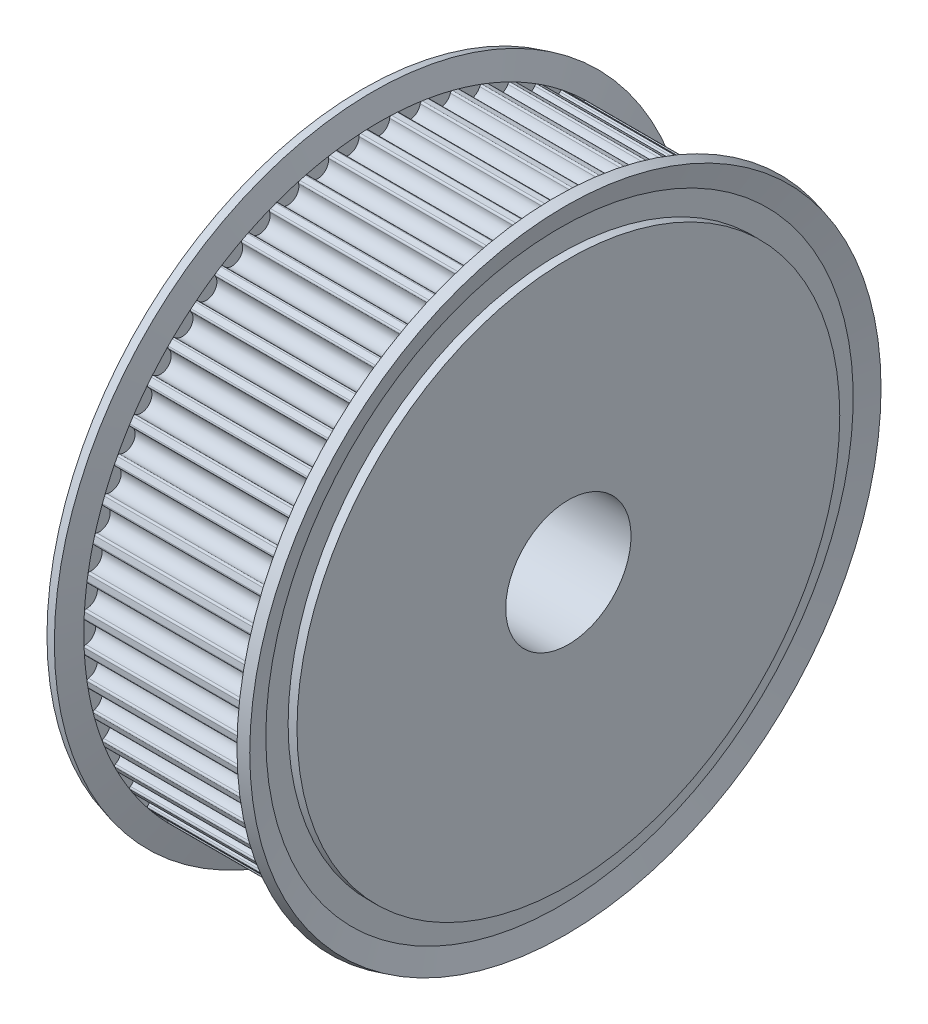
SolidWorks part; units mm, degrees
ref_plane "Front Plane" through (0, 0, 0) normal (0, 0, 1) x (1, 0, 0)
ref_plane "Top Plane" through (0, 0, 0) normal (0, 1, 0) x (1, 0, 0)
ref_plane "Right Plane" through (0, 0, 0) normal (1, 0, 0) x (0, 0, -1)
ref_plane "Plane1" through (0, 0, 0) normal (0, 0, 1) x (1, 0, 0)
sketch "Sketch1" plane through (0, 0, 0) normal (0, 0, 1) x (1, 0, 0)
  line L0 (0, 0) -> (0, 26)
  line L1 (0, 26) -> (0.85, 26)
  line L2 (0.85, 26) -> (0.85, 28.1383)
  line L3 (0.85, 28.1383) -> (0.2865, 30.2412)
  line L4 (0.2865, 30.2412) -> (1.2525, 30.5)
  line L5 (1.2525, 30.5) -> (1.85, 28.27)
  line L6 (1.85, 28.27) -> (18.15, 28.27)
  line L7 (18.15, 28.27) -> (18.7475, 30.5)
  line L8 (18.7475, 30.5) -> (19.7135, 30.2412)
  line L9 (19.7135, 30.2412) -> (19.15, 28.1383)
  line L10 (19.15, 28.1383) -> (19.15, 26)
  line L11 (19.15, 26) -> (20, 26)
  line L12 (20, 26) -> (20, 0)
  line L13 (20, 0) -> (0, 0)
  line L14 (20, 0) -> (0, 0) construction
revolve "Revolve1" add sketch "Sketch1" angle 360 about L14 reverse direction yes
ref_plane "Plane2" through (10, 0, 0) normal (1, 0, 0) x (0, 0, -1)
sketch "Sketch2" plane through (10, 0, 0) normal (1, 0, 0) x (0, 0, -1)
  line L0 (-1.2204, 28.624) -> (-1.2042, 28.2443)
  line L1 (1.2042, 28.2443) -> (1.2204, 28.624)
  arc A0 (-1.2042, 28.2443) -> (-1.0274, 28.0866) centre (-1.1969, 28.0745) cw
  arc A1 (-1.0274, 28.0866) -> (1.0274, 28.0866) centre (0, 28.16) ccw
  arc A2 (1.0274, 28.0866) -> (1.2042, 28.2443) centre (1.1969, 28.0745) cw
  arc A3 (1.2204, 28.624) -> (-1.2204, 28.624) centre (0, 0) ccw
extrude "Cut-Extrude1" cut sketch "Sketch2" against normal blind 8.15 and the other way blind 8.15
ref_plane "Plane3" through (10, 0, 0) normal (1, 0, 0) x (0, 0, -1)
sketch "Sketch3" plane through (10, 0, 0) normal (1, 0, 0) x (0, 0, -1)
  line L0 (-4.2057, 28.3396) -> (-4.1499, 27.9637)
  line L1 (-1.7547, 28.2155) -> (-1.7783, 28.5948)
  arc A0 (-4.1499, 27.9637) -> (-3.9576, 27.8254) centre (-4.125, 27.7956) cw
  arc A1 (-3.9576, 27.8254) -> (-1.9141, 28.0401) centre (-2.9435, 28.0057) ccw
  arc A2 (-1.9141, 28.0401) -> (-1.7547, 28.2155) centre (-1.7442, 28.0458) cw
  arc A3 (-1.7783, 28.5948) -> (-4.2057, 28.3396) centre (0, 0) ccw
extrude "Cut-Extrude2" cut sketch "Sketch3" against normal blind 8.15 and the other way blind 8.15
ref_plane "Plane4" through (10, 0, 0) normal (1, 0, 0) x (0, 0, -1)
sketch "Sketch4" plane through (10, 0, 0) normal (1, 0, 0) x (0, 0, -1)
  line L0 (-7.145, 27.7448) -> (-7.0502, 27.3768)
  line L1 (-4.6945, 27.8775) -> (-4.7576, 28.2522)
  arc A0 (-7.0502, 27.3768) -> (-6.8445, 27.2592) centre (-7.0078, 27.2121) cw
  arc A1 (-6.8445, 27.2592) -> (-4.8346, 27.6865) centre (-5.8548, 27.5446) ccw
  arc A2 (-4.8346, 27.6865) -> (-4.6945, 27.8775) centre (-4.6662, 27.7099) cw
  arc A3 (-4.7576, 28.2522) -> (-7.145, 27.7448) centre (0, 0) ccw
extrude "Cut-Extrude3" cut sketch "Sketch4" against normal blind 8.15 and the other way blind 8.15
ref_plane "Plane5" through (10, 0, 0) normal (1, 0, 0) x (0, 0, -1)
sketch "Sketch5" plane through (10, 0, 0) normal (1, 0, 0) x (0, 0, -1)
  line L0 (-10.0059, 26.8459) -> (-9.8732, 26.4898)
  line L1 (-7.5827, 27.2341) -> (-7.6847, 27.6002)
  arc A0 (-9.8732, 26.4898) -> (-9.6563, 26.3945) centre (-9.8139, 26.3306) cw
  arc A1 (-9.6563, 26.3945) -> (-7.7021, 27.0294) centre (-8.7019, 26.7818) ccw
  arc A2 (-7.7021, 27.0294) -> (-7.5827, 27.2341) centre (-7.5371, 27.0703) cw
  arc A3 (-7.6847, 27.6002) -> (-10.0059, 26.8459) centre (0, 0) ccw
extrude "Cut-Extrude4" cut sketch "Sketch5" against normal blind 8.15 and the other way blind 8.15
ref_plane "Plane6" through (10, 0, 0) normal (1, 0, 0) x (0, 0, -1)
sketch "Sketch6" plane through (10, 0, 0) normal (1, 0, 0) x (0, 0, -1)
  line L0 (-12.7573, 25.6529) -> (-12.5881, 25.3127)
  line L1 (-10.3879, 26.2923) -> (-10.5276, 26.6457)
  arc A0 (-12.5881, 25.3127) -> (-12.3624, 25.2405) centre (-12.5124, 25.1605) cw
  arc A1 (-12.3624, 25.2405) -> (-10.4853, 26.0763) centre (-11.4537, 25.7254) ccw
  arc A2 (-10.4853, 26.0763) -> (-10.3879, 26.2923) centre (-10.3255, 26.1342) cw
  arc A3 (-10.5276, 26.6457) -> (-12.7573, 25.6529) centre (0, 0) ccw
extrude "Cut-Extrude5" cut sketch "Sketch6" against normal blind 8.15 and the other way blind 8.15
ref_plane "Plane7" through (10, 0, 0) normal (1, 0, 0) x (0, 0, -1)
sketch "Sketch7" plane through (10, 0, 0) normal (1, 0, 0) x (0, 0, -1)
  line L0 (-15.3689, 24.1789) -> (-15.165, 23.8582)
  line L1 (-13.0793, 25.0624) -> (-13.2551, 25.3993)
  arc A0 (-15.165, 23.8582) -> (-14.933, 23.81) centre (-15.0738, 23.7148) cw
  arc A1 (-14.933, 23.81) -> (-13.1536, 24.8374) centre (-14.08, 24.3873) ccw
  arc A2 (-13.1536, 24.8374) -> (-13.0793, 25.0624) centre (-13.0007, 24.9117) cw
  arc A3 (-13.2551, 25.3993) -> (-15.3689, 24.1789) centre (0, 0) ccw
extrude "Cut-Extrude6" cut sketch "Sketch7" against normal blind 8.15 and the other way blind 8.15
ref_plane "Plane8" through (10, 0, 0) normal (1, 0, 0) x (0, 0, -1)
sketch "Sketch8" plane through (10, 0, 0) normal (1, 0, 0) x (0, 0, -1)
  line L0 (-17.8121, 22.44) -> (-17.5758, 22.1423)
  line L1 (-15.6274, 23.558) -> (-15.8375, 23.8746)
  arc A0 (-17.5758, 22.1423) -> (-17.3401, 22.1187) centre (-17.4701, 22.0092) cw
  arc A1 (-17.3401, 22.1187) -> (-15.6777, 23.3264) centre (-16.552, 22.7819) ccw
  arc A2 (-15.6777, 23.3264) -> (-15.6274, 23.558) centre (-15.5334, 23.4163) cw
  arc A3 (-15.8375, 23.8746) -> (-17.8121, 22.44) centre (0, 0) ccw
extrude "Cut-Extrude7" cut sketch "Sketch8" against normal blind 8.15 and the other way blind 8.15
ref_plane "Plane9" through (10, 0, 0) normal (1, 0, 0) x (0, 0, -1)
sketch "Sketch9" plane through (10, 0, 0) normal (1, 0, 0) x (0, 0, -1)
  line L0 (-20.0601, 20.4552) -> (-19.794, 20.1839)
  line L1 (-18.0043, 21.7954) -> (-18.2463, 22.0884)
  arc A0 (-19.794, 20.1839) -> (-19.5571, 20.185) centre (-19.675, 20.0625) cw
  arc A1 (-19.5571, 20.185) -> (-18.0301, 21.5599) centre (-18.8427, 20.927) ccw
  arc A2 (-18.0301, 21.5599) -> (-18.0043, 21.7954) centre (-17.896, 21.6643) cw
  arc A3 (-18.2463, 22.0884) -> (-20.0601, 20.4552) centre (0, 0) ccw
extrude "Cut-Extrude8" cut sketch "Sketch9" against normal blind 8.15 and the other way blind 8.15
ref_plane "Plane10" through (10, 0, 0) normal (1, 0, 0) x (0, 0, -1)
sketch "Sketch10" plane through (10, 0, 0) normal (1, 0, 0) x (0, 0, -1)
  line L0 (-22.0884, 18.2463) -> (-21.7954, 18.0043)
  line L1 (-20.1839, 19.794) -> (-20.4552, 20.0601)
  arc A0 (-21.7954, 18.0043) -> (-21.5599, 18.0301) centre (-21.6643, 17.896) cw
  arc A1 (-21.5599, 18.0301) -> (-20.185, 19.5571) centre (-20.927, 18.8427) ccw
  arc A2 (-20.185, 19.5571) -> (-20.1839, 19.794) centre (-20.0625, 19.675) cw
  arc A3 (-20.4552, 20.0601) -> (-22.0884, 18.2463) centre (0, 0) ccw
extrude "Cut-Extrude9" cut sketch "Sketch10" against normal blind 8.15 and the other way blind 8.15
ref_plane "Plane11" through (10, 0, 0) normal (1, 0, 0) x (0, 0, -1)
sketch "Sketch11" plane through (10, 0, 0) normal (1, 0, 0) x (0, 0, -1)
  line L0 (-23.8746, 15.8375) -> (-23.558, 15.6274)
  line L1 (-22.1423, 17.5758) -> (-22.44, 17.8121)
  arc A0 (-23.558, 15.6274) -> (-23.3264, 15.6777) centre (-23.4163, 15.5334) cw
  arc A1 (-23.3264, 15.6777) -> (-22.1187, 17.3401) centre (-22.7819, 16.552) ccw
  arc A2 (-22.1187, 17.3401) -> (-22.1423, 17.5758) centre (-22.0092, 17.4701) cw
  arc A3 (-22.44, 17.8121) -> (-23.8746, 15.8375) centre (0, 0) ccw
extrude "Cut-Extrude10" cut sketch "Sketch11" against normal blind 8.15 and the other way blind 8.15
ref_plane "Plane12" through (10, 0, 0) normal (1, 0, 0) x (0, 0, -1)
sketch "Sketch12" plane through (10, 0, 0) normal (1, 0, 0) x (0, 0, -1)
  line L0 (-25.3993, 13.2551) -> (-25.0624, 13.0793)
  line L1 (-23.8582, 15.165) -> (-24.1789, 15.3689)
  arc A0 (-25.0624, 13.0793) -> (-24.8374, 13.1536) centre (-24.9117, 13.0007) cw
  arc A1 (-24.8374, 13.1536) -> (-23.81, 14.933) centre (-24.3873, 14.08) ccw
  arc A2 (-23.81, 14.933) -> (-23.8582, 15.165) centre (-23.7148, 15.0738) cw
  arc A3 (-24.1789, 15.3689) -> (-25.3993, 13.2551) centre (0, 0) ccw
extrude "Cut-Extrude11" cut sketch "Sketch12" against normal blind 8.15 and the other way blind 8.15
ref_plane "Plane13" through (10, 0, 0) normal (1, 0, 0) x (0, 0, -1)
sketch "Sketch13" plane through (10, 0, 0) normal (1, 0, 0) x (0, 0, -1)
  line L0 (-26.6457, 10.5276) -> (-26.2923, 10.3879)
  line L1 (-25.3127, 12.5881) -> (-25.6529, 12.7573)
  arc A0 (-26.2923, 10.3879) -> (-26.0763, 10.4853) centre (-26.1342, 10.3255) cw
  arc A1 (-26.0763, 10.4853) -> (-25.2405, 12.3624) centre (-25.7254, 11.4537) ccw
  arc A2 (-25.2405, 12.3624) -> (-25.3127, 12.5881) centre (-25.1605, 12.5124) cw
  arc A3 (-25.6529, 12.7573) -> (-26.6457, 10.5276) centre (0, 0) ccw
extrude "Cut-Extrude12" cut sketch "Sketch13" against normal blind 8.15 and the other way blind 8.15
ref_plane "Plane14" through (10, 0, 0) normal (1, 0, 0) x (0, 0, -1)
sketch "Sketch14" plane through (10, 0, 0) normal (1, 0, 0) x (0, 0, -1)
  line L0 (-27.6002, 7.6847) -> (-27.2341, 7.5827)
  line L1 (-26.4898, 9.8732) -> (-26.8459, 10.0059)
  arc A0 (-27.2341, 7.5827) -> (-27.0294, 7.7021) centre (-27.0703, 7.5371) cw
  arc A1 (-27.0294, 7.7021) -> (-26.3945, 9.6563) centre (-26.7818, 8.7019) ccw
  arc A2 (-26.3945, 9.6563) -> (-26.4898, 9.8732) centre (-26.3306, 9.8139) cw
  arc A3 (-26.8459, 10.0059) -> (-27.6002, 7.6847) centre (0, 0) ccw
extrude "Cut-Extrude13" cut sketch "Sketch14" against normal blind 8.15 and the other way blind 8.15
ref_plane "Plane15" through (10, 0, 0) normal (1, 0, 0) x (0, 0, -1)
sketch "Sketch15" plane through (10, 0, 0) normal (1, 0, 0) x (0, 0, -1)
  line L0 (-28.2522, 4.7576) -> (-27.8775, 4.6945)
  line L1 (-27.3768, 7.0502) -> (-27.7448, 7.145)
  arc A0 (-27.8775, 4.6945) -> (-27.6865, 4.8346) centre (-27.7099, 4.6662) cw
  arc A1 (-27.6865, 4.8346) -> (-27.2592, 6.8445) centre (-27.5446, 5.8548) ccw
  arc A2 (-27.2592, 6.8445) -> (-27.3768, 7.0502) centre (-27.2121, 7.0078) cw
  arc A3 (-27.7448, 7.145) -> (-28.2522, 4.7576) centre (0, 0) ccw
extrude "Cut-Extrude14" cut sketch "Sketch15" against normal blind 8.15 and the other way blind 8.15
ref_plane "Plane16" through (10, 0, 0) normal (1, 0, 0) x (0, 0, -1)
sketch "Sketch16" plane through (10, 0, 0) normal (1, 0, 0) x (0, 0, -1)
  line L0 (-28.5948, 1.7783) -> (-28.2155, 1.7547)
  line L1 (-27.9637, 4.1499) -> (-28.3396, 4.2057)
  arc A0 (-28.2155, 1.7547) -> (-28.0401, 1.9141) centre (-28.0458, 1.7442) cw
  arc A1 (-28.0401, 1.9141) -> (-27.8254, 3.9576) centre (-28.0057, 2.9435) ccw
  arc A2 (-27.8254, 3.9576) -> (-27.9637, 4.1499) centre (-27.7956, 4.125) cw
  arc A3 (-28.3396, 4.2057) -> (-28.5948, 1.7783) centre (0, 0) ccw
extrude "Cut-Extrude15" cut sketch "Sketch16" against normal blind 8.15 and the other way blind 8.15
ref_plane "Plane17" through (10, 0, 0) normal (1, 0, 0) x (0, 0, -1)
sketch "Sketch17" plane through (10, 0, 0) normal (1, 0, 0) x (0, 0, -1)
  line L0 (-28.624, -1.2204) -> (-28.2443, -1.2042)
  line L1 (-28.2443, 1.2042) -> (-28.624, 1.2204)
  arc A0 (-28.2443, -1.2042) -> (-28.0866, -1.0274) centre (-28.0745, -1.1969) cw
  arc A1 (-28.0866, -1.0274) -> (-28.0866, 1.0274) centre (-28.16, 0) ccw
  arc A2 (-28.0866, 1.0274) -> (-28.2443, 1.2042) centre (-28.0745, 1.1969) cw
  arc A3 (-28.624, 1.2204) -> (-28.624, -1.2204) centre (0, 0) ccw
extrude "Cut-Extrude16" cut sketch "Sketch17" against normal blind 8.15 and the other way blind 8.15
ref_plane "Plane18" through (10, 0, 0) normal (1, 0, 0) x (0, 0, -1)
sketch "Sketch18" plane through (10, 0, 0) normal (1, 0, 0) x (0, 0, -1)
  line L0 (-28.3396, -4.2057) -> (-27.9637, -4.1499)
  line L1 (-28.2155, -1.7547) -> (-28.5948, -1.7783)
  arc A0 (-27.9637, -4.1499) -> (-27.8254, -3.9576) centre (-27.7956, -4.125) cw
  arc A1 (-27.8254, -3.9576) -> (-28.0401, -1.9141) centre (-28.0057, -2.9435) ccw
  arc A2 (-28.0401, -1.9141) -> (-28.2155, -1.7547) centre (-28.0458, -1.7442) cw
  arc A3 (-28.5948, -1.7783) -> (-28.3396, -4.2057) centre (0, 0) ccw
extrude "Cut-Extrude17" cut sketch "Sketch18" against normal blind 8.15 and the other way blind 8.15
ref_plane "Plane19" through (10, 0, 0) normal (1, 0, 0) x (0, 0, -1)
sketch "Sketch19" plane through (10, 0, 0) normal (1, 0, 0) x (0, 0, -1)
  line L0 (-27.7448, -7.145) -> (-27.3768, -7.0502)
  line L1 (-27.8775, -4.6945) -> (-28.2522, -4.7576)
  arc A0 (-27.3768, -7.0502) -> (-27.2592, -6.8445) centre (-27.2121, -7.0078) cw
  arc A1 (-27.2592, -6.8445) -> (-27.6865, -4.8346) centre (-27.5446, -5.8548) ccw
  arc A2 (-27.6865, -4.8346) -> (-27.8775, -4.6945) centre (-27.7099, -4.6662) cw
  arc A3 (-28.2522, -4.7576) -> (-27.7448, -7.145) centre (0, 0) ccw
extrude "Cut-Extrude18" cut sketch "Sketch19" against normal blind 8.15 and the other way blind 8.15
ref_plane "Plane20" through (10, 0, 0) normal (1, 0, 0) x (0, 0, -1)
sketch "Sketch20" plane through (10, 0, 0) normal (1, 0, 0) x (0, 0, -1)
  line L0 (-26.8459, -10.0059) -> (-26.4898, -9.8732)
  line L1 (-27.2341, -7.5827) -> (-27.6002, -7.6847)
  arc A0 (-26.4898, -9.8732) -> (-26.3945, -9.6563) centre (-26.3306, -9.8139) cw
  arc A1 (-26.3945, -9.6563) -> (-27.0294, -7.7021) centre (-26.7818, -8.7019) ccw
  arc A2 (-27.0294, -7.7021) -> (-27.2341, -7.5827) centre (-27.0703, -7.5371) cw
  arc A3 (-27.6002, -7.6847) -> (-26.8459, -10.0059) centre (0, 0) ccw
extrude "Cut-Extrude19" cut sketch "Sketch20" against normal blind 8.15 and the other way blind 8.15
ref_plane "Plane21" through (10, 0, 0) normal (1, 0, 0) x (0, 0, -1)
sketch "Sketch21" plane through (10, 0, 0) normal (1, 0, 0) x (0, 0, -1)
  line L0 (-25.6529, -12.7573) -> (-25.3127, -12.5881)
  line L1 (-26.2923, -10.3879) -> (-26.6457, -10.5276)
  arc A0 (-25.3127, -12.5881) -> (-25.2405, -12.3624) centre (-25.1605, -12.5124) cw
  arc A1 (-25.2405, -12.3624) -> (-26.0763, -10.4853) centre (-25.7254, -11.4537) ccw
  arc A2 (-26.0763, -10.4853) -> (-26.2923, -10.3879) centre (-26.1342, -10.3255) cw
  arc A3 (-26.6457, -10.5276) -> (-25.6529, -12.7573) centre (0, 0) ccw
extrude "Cut-Extrude20" cut sketch "Sketch21" against normal blind 8.15 and the other way blind 8.15
ref_plane "Plane22" through (10, 0, 0) normal (1, 0, 0) x (0, 0, -1)
sketch "Sketch22" plane through (10, 0, 0) normal (1, 0, 0) x (0, 0, -1)
  line L0 (-24.1789, -15.3689) -> (-23.8582, -15.165)
  line L1 (-25.0624, -13.0793) -> (-25.3993, -13.2551)
  arc A0 (-23.8582, -15.165) -> (-23.81, -14.933) centre (-23.7148, -15.0738) cw
  arc A1 (-23.81, -14.933) -> (-24.8374, -13.1536) centre (-24.3873, -14.08) ccw
  arc A2 (-24.8374, -13.1536) -> (-25.0624, -13.0793) centre (-24.9117, -13.0007) cw
  arc A3 (-25.3993, -13.2551) -> (-24.1789, -15.3689) centre (0, 0) ccw
extrude "Cut-Extrude21" cut sketch "Sketch22" against normal blind 8.15 and the other way blind 8.15
ref_plane "Plane23" through (10, 0, 0) normal (1, 0, 0) x (0, 0, -1)
sketch "Sketch23" plane through (10, 0, 0) normal (1, 0, 0) x (0, 0, -1)
  line L0 (-22.44, -17.8121) -> (-22.1423, -17.5758)
  line L1 (-23.558, -15.6274) -> (-23.8746, -15.8375)
  arc A0 (-22.1423, -17.5758) -> (-22.1187, -17.3401) centre (-22.0092, -17.4701) cw
  arc A1 (-22.1187, -17.3401) -> (-23.3264, -15.6777) centre (-22.7819, -16.552) ccw
  arc A2 (-23.3264, -15.6777) -> (-23.558, -15.6274) centre (-23.4163, -15.5334) cw
  arc A3 (-23.8746, -15.8375) -> (-22.44, -17.8121) centre (0, 0) ccw
extrude "Cut-Extrude22" cut sketch "Sketch23" against normal blind 8.15 and the other way blind 8.15
ref_plane "Plane24" through (10, 0, 0) normal (1, 0, 0) x (0, 0, -1)
sketch "Sketch24" plane through (10, 0, 0) normal (1, 0, 0) x (0, 0, -1)
  line L0 (-20.4552, -20.0601) -> (-20.1839, -19.794)
  line L1 (-21.7954, -18.0043) -> (-22.0884, -18.2463)
  arc A0 (-20.1839, -19.794) -> (-20.185, -19.5571) centre (-20.0625, -19.675) cw
  arc A1 (-20.185, -19.5571) -> (-21.5599, -18.0301) centre (-20.927, -18.8427) ccw
  arc A2 (-21.5599, -18.0301) -> (-21.7954, -18.0043) centre (-21.6643, -17.896) cw
  arc A3 (-22.0884, -18.2463) -> (-20.4552, -20.0601) centre (0, 0) ccw
extrude "Cut-Extrude23" cut sketch "Sketch24" against normal blind 8.15 and the other way blind 8.15
ref_plane "Plane25" through (10, 0, 0) normal (1, 0, 0) x (0, 0, -1)
sketch "Sketch25" plane through (10, 0, 0) normal (1, 0, 0) x (0, 0, -1)
  line L0 (-18.2463, -22.0884) -> (-18.0043, -21.7954)
  line L1 (-19.794, -20.1839) -> (-20.0601, -20.4552)
  arc A0 (-18.0043, -21.7954) -> (-18.0301, -21.5599) centre (-17.896, -21.6643) cw
  arc A1 (-18.0301, -21.5599) -> (-19.5571, -20.185) centre (-18.8427, -20.927) ccw
  arc A2 (-19.5571, -20.185) -> (-19.794, -20.1839) centre (-19.675, -20.0625) cw
  arc A3 (-20.0601, -20.4552) -> (-18.2463, -22.0884) centre (0, 0) ccw
extrude "Cut-Extrude24" cut sketch "Sketch25" against normal blind 8.15 and the other way blind 8.15
ref_plane "Plane26" through (10, 0, 0) normal (1, 0, 0) x (0, 0, -1)
sketch "Sketch26" plane through (10, 0, 0) normal (1, 0, 0) x (0, 0, -1)
  line L0 (-15.8375, -23.8746) -> (-15.6274, -23.558)
  line L1 (-17.5758, -22.1423) -> (-17.8121, -22.44)
  arc A0 (-15.6274, -23.558) -> (-15.6777, -23.3264) centre (-15.5334, -23.4163) cw
  arc A1 (-15.6777, -23.3264) -> (-17.3401, -22.1187) centre (-16.552, -22.7819) ccw
  arc A2 (-17.3401, -22.1187) -> (-17.5758, -22.1423) centre (-17.4701, -22.0092) cw
  arc A3 (-17.8121, -22.44) -> (-15.8375, -23.8746) centre (0, 0) ccw
extrude "Cut-Extrude25" cut sketch "Sketch26" against normal blind 8.15 and the other way blind 8.15
ref_plane "Plane27" through (10, 0, 0) normal (1, 0, 0) x (0, 0, -1)
sketch "Sketch27" plane through (10, 0, 0) normal (1, 0, 0) x (0, 0, -1)
  line L0 (-13.2551, -25.3993) -> (-13.0793, -25.0624)
  line L1 (-15.165, -23.8582) -> (-15.3689, -24.1789)
  arc A0 (-13.0793, -25.0624) -> (-13.1536, -24.8374) centre (-13.0007, -24.9117) cw
  arc A1 (-13.1536, -24.8374) -> (-14.933, -23.81) centre (-14.08, -24.3873) ccw
  arc A2 (-14.933, -23.81) -> (-15.165, -23.8582) centre (-15.0738, -23.7148) cw
  arc A3 (-15.3689, -24.1789) -> (-13.2551, -25.3993) centre (0, 0) ccw
extrude "Cut-Extrude26" cut sketch "Sketch27" against normal blind 8.15 and the other way blind 8.15
ref_plane "Plane28" through (10, 0, 0) normal (1, 0, 0) x (0, 0, -1)
sketch "Sketch28" plane through (10, 0, 0) normal (1, 0, 0) x (0, 0, -1)
  line L0 (-10.5276, -26.6457) -> (-10.3879, -26.2923)
  line L1 (-12.5881, -25.3127) -> (-12.7573, -25.6529)
  arc A0 (-10.3879, -26.2923) -> (-10.4853, -26.0763) centre (-10.3255, -26.1342) cw
  arc A1 (-10.4853, -26.0763) -> (-12.3624, -25.2405) centre (-11.4537, -25.7254) ccw
  arc A2 (-12.3624, -25.2405) -> (-12.5881, -25.3127) centre (-12.5124, -25.1605) cw
  arc A3 (-12.7573, -25.6529) -> (-10.5276, -26.6457) centre (0, 0) ccw
extrude "Cut-Extrude27" cut sketch "Sketch28" against normal blind 8.15 and the other way blind 8.15
ref_plane "Plane29" through (10, 0, 0) normal (1, 0, 0) x (0, 0, -1)
sketch "Sketch29" plane through (10, 0, 0) normal (1, 0, 0) x (0, 0, -1)
  line L0 (-7.6847, -27.6002) -> (-7.5827, -27.2341)
  line L1 (-9.8732, -26.4898) -> (-10.0059, -26.8459)
  arc A0 (-7.5827, -27.2341) -> (-7.7021, -27.0294) centre (-7.5371, -27.0703) cw
  arc A1 (-7.7021, -27.0294) -> (-9.6563, -26.3945) centre (-8.7019, -26.7818) ccw
  arc A2 (-9.6563, -26.3945) -> (-9.8732, -26.4898) centre (-9.8139, -26.3306) cw
  arc A3 (-10.0059, -26.8459) -> (-7.6847, -27.6002) centre (0, 0) ccw
extrude "Cut-Extrude28" cut sketch "Sketch29" against normal blind 8.15 and the other way blind 8.15
ref_plane "Plane30" through (10, 0, 0) normal (1, 0, 0) x (0, 0, -1)
sketch "Sketch30" plane through (10, 0, 0) normal (1, 0, 0) x (0, 0, -1)
  line L0 (-4.7576, -28.2522) -> (-4.6945, -27.8775)
  line L1 (-7.0502, -27.3768) -> (-7.145, -27.7448)
  arc A0 (-4.6945, -27.8775) -> (-4.8346, -27.6865) centre (-4.6662, -27.7099) cw
  arc A1 (-4.8346, -27.6865) -> (-6.8445, -27.2592) centre (-5.8548, -27.5446) ccw
  arc A2 (-6.8445, -27.2592) -> (-7.0502, -27.3768) centre (-7.0078, -27.2121) cw
  arc A3 (-7.145, -27.7448) -> (-4.7576, -28.2522) centre (0, 0) ccw
extrude "Cut-Extrude29" cut sketch "Sketch30" against normal blind 8.15 and the other way blind 8.15
ref_plane "Plane31" through (10, 0, 0) normal (1, 0, 0) x (0, 0, -1)
sketch "Sketch31" plane through (10, 0, 0) normal (1, 0, 0) x (0, 0, -1)
  line L0 (-1.7783, -28.5948) -> (-1.7547, -28.2155)
  line L1 (-4.1499, -27.9637) -> (-4.2057, -28.3396)
  arc A0 (-1.7547, -28.2155) -> (-1.9141, -28.0401) centre (-1.7442, -28.0458) cw
  arc A1 (-1.9141, -28.0401) -> (-3.9576, -27.8254) centre (-2.9435, -28.0057) ccw
  arc A2 (-3.9576, -27.8254) -> (-4.1499, -27.9637) centre (-4.125, -27.7956) cw
  arc A3 (-4.2057, -28.3396) -> (-1.7783, -28.5948) centre (0, 0) ccw
extrude "Cut-Extrude30" cut sketch "Sketch31" against normal blind 8.15 and the other way blind 8.15
ref_plane "Plane32" through (10, 0, 0) normal (1, 0, 0) x (0, 0, -1)
sketch "Sketch32" plane through (10, 0, 0) normal (1, 0, 0) x (0, 0, -1)
  line L0 (1.2204, -28.624) -> (1.2042, -28.2443)
  line L1 (-1.2042, -28.2443) -> (-1.2204, -28.624)
  arc A0 (1.2042, -28.2443) -> (1.0274, -28.0866) centre (1.1969, -28.0745) cw
  arc A1 (1.0274, -28.0866) -> (-1.0274, -28.0866) centre (0, -28.16) ccw
  arc A2 (-1.0274, -28.0866) -> (-1.2042, -28.2443) centre (-1.1969, -28.0745) cw
  arc A3 (-1.2204, -28.624) -> (1.2204, -28.624) centre (0, 0) ccw
extrude "Cut-Extrude31" cut sketch "Sketch32" against normal blind 8.15 and the other way blind 8.15
ref_plane "Plane33" through (10, 0, 0) normal (1, 0, 0) x (0, 0, -1)
sketch "Sketch33" plane through (10, 0, 0) normal (1, 0, 0) x (0, 0, -1)
  line L0 (4.2057, -28.3396) -> (4.1499, -27.9637)
  line L1 (1.7547, -28.2155) -> (1.7783, -28.5948)
  arc A0 (4.1499, -27.9637) -> (3.9576, -27.8254) centre (4.125, -27.7956) cw
  arc A1 (3.9576, -27.8254) -> (1.9141, -28.0401) centre (2.9435, -28.0057) ccw
  arc A2 (1.9141, -28.0401) -> (1.7547, -28.2155) centre (1.7442, -28.0458) cw
  arc A3 (1.7783, -28.5948) -> (4.2057, -28.3396) centre (0, 0) ccw
extrude "Cut-Extrude32" cut sketch "Sketch33" against normal blind 8.15 and the other way blind 8.15
ref_plane "Plane34" through (10, 0, 0) normal (1, 0, 0) x (0, 0, -1)
sketch "Sketch34" plane through (10, 0, 0) normal (1, 0, 0) x (0, 0, -1)
  line L0 (7.145, -27.7448) -> (7.0502, -27.3768)
  line L1 (4.6945, -27.8775) -> (4.7576, -28.2522)
  arc A0 (7.0502, -27.3768) -> (6.8445, -27.2592) centre (7.0078, -27.2121) cw
  arc A1 (6.8445, -27.2592) -> (4.8346, -27.6865) centre (5.8548, -27.5446) ccw
  arc A2 (4.8346, -27.6865) -> (4.6945, -27.8775) centre (4.6662, -27.7099) cw
  arc A3 (4.7576, -28.2522) -> (7.145, -27.7448) centre (0, 0) ccw
extrude "Cut-Extrude33" cut sketch "Sketch34" against normal blind 8.15 and the other way blind 8.15
ref_plane "Plane35" through (10, 0, 0) normal (1, 0, 0) x (0, 0, -1)
sketch "Sketch35" plane through (10, 0, 0) normal (1, 0, 0) x (0, 0, -1)
  line L0 (10.0059, -26.8459) -> (9.8732, -26.4898)
  line L1 (7.5827, -27.2341) -> (7.6847, -27.6002)
  arc A0 (9.8732, -26.4898) -> (9.6563, -26.3945) centre (9.8139, -26.3306) cw
  arc A1 (9.6563, -26.3945) -> (7.7021, -27.0294) centre (8.7019, -26.7818) ccw
  arc A2 (7.7021, -27.0294) -> (7.5827, -27.2341) centre (7.5371, -27.0703) cw
  arc A3 (7.6847, -27.6002) -> (10.0059, -26.8459) centre (0, 0) ccw
extrude "Cut-Extrude34" cut sketch "Sketch35" against normal blind 8.15 and the other way blind 8.15
ref_plane "Plane36" through (10, 0, 0) normal (1, 0, 0) x (0, 0, -1)
sketch "Sketch36" plane through (10, 0, 0) normal (1, 0, 0) x (0, 0, -1)
  line L0 (12.7573, -25.6529) -> (12.5881, -25.3127)
  line L1 (10.3879, -26.2923) -> (10.5276, -26.6457)
  arc A0 (12.5881, -25.3127) -> (12.3624, -25.2405) centre (12.5124, -25.1605) cw
  arc A1 (12.3624, -25.2405) -> (10.4853, -26.0763) centre (11.4537, -25.7254) ccw
  arc A2 (10.4853, -26.0763) -> (10.3879, -26.2923) centre (10.3255, -26.1342) cw
  arc A3 (10.5276, -26.6457) -> (12.7573, -25.6529) centre (0, 0) ccw
extrude "Cut-Extrude35" cut sketch "Sketch36" against normal blind 8.15 and the other way blind 8.15
ref_plane "Plane37" through (10, 0, 0) normal (1, 0, 0) x (0, 0, -1)
sketch "Sketch37" plane through (10, 0, 0) normal (1, 0, 0) x (0, 0, -1)
  line L0 (15.3689, -24.1789) -> (15.165, -23.8582)
  line L1 (13.0793, -25.0624) -> (13.2551, -25.3993)
  arc A0 (15.165, -23.8582) -> (14.933, -23.81) centre (15.0738, -23.7148) cw
  arc A1 (14.933, -23.81) -> (13.1536, -24.8374) centre (14.08, -24.3873) ccw
  arc A2 (13.1536, -24.8374) -> (13.0793, -25.0624) centre (13.0007, -24.9117) cw
  arc A3 (13.2551, -25.3993) -> (15.3689, -24.1789) centre (0, 0) ccw
extrude "Cut-Extrude36" cut sketch "Sketch37" against normal blind 8.15 and the other way blind 8.15
ref_plane "Plane38" through (10, 0, 0) normal (1, 0, 0) x (0, 0, -1)
sketch "Sketch38" plane through (10, 0, 0) normal (1, 0, 0) x (0, 0, -1)
  line L0 (17.8121, -22.44) -> (17.5758, -22.1423)
  line L1 (15.6274, -23.558) -> (15.8375, -23.8746)
  arc A0 (17.5758, -22.1423) -> (17.3401, -22.1187) centre (17.4701, -22.0092) cw
  arc A1 (17.3401, -22.1187) -> (15.6777, -23.3264) centre (16.552, -22.7819) ccw
  arc A2 (15.6777, -23.3264) -> (15.6274, -23.558) centre (15.5334, -23.4163) cw
  arc A3 (15.8375, -23.8746) -> (17.8121, -22.44) centre (0, 0) ccw
extrude "Cut-Extrude37" cut sketch "Sketch38" against normal blind 8.15 and the other way blind 8.15
ref_plane "Plane39" through (10, 0, 0) normal (1, 0, 0) x (0, 0, -1)
sketch "Sketch39" plane through (10, 0, 0) normal (1, 0, 0) x (0, 0, -1)
  line L0 (20.0601, -20.4552) -> (19.794, -20.1839)
  line L1 (18.0043, -21.7954) -> (18.2463, -22.0884)
  arc A0 (19.794, -20.1839) -> (19.5571, -20.185) centre (19.675, -20.0625) cw
  arc A1 (19.5571, -20.185) -> (18.0301, -21.5599) centre (18.8427, -20.927) ccw
  arc A2 (18.0301, -21.5599) -> (18.0043, -21.7954) centre (17.896, -21.6643) cw
  arc A3 (18.2463, -22.0884) -> (20.0601, -20.4552) centre (0, 0) ccw
extrude "Cut-Extrude38" cut sketch "Sketch39" against normal blind 8.15 and the other way blind 8.15
ref_plane "Plane40" through (10, 0, 0) normal (1, 0, 0) x (0, 0, -1)
sketch "Sketch40" plane through (10, 0, 0) normal (1, 0, 0) x (0, 0, -1)
  line L0 (22.0884, -18.2463) -> (21.7954, -18.0043)
  line L1 (20.1839, -19.794) -> (20.4552, -20.0601)
  arc A0 (21.7954, -18.0043) -> (21.5599, -18.0301) centre (21.6643, -17.896) cw
  arc A1 (21.5599, -18.0301) -> (20.185, -19.5571) centre (20.927, -18.8427) ccw
  arc A2 (20.185, -19.5571) -> (20.1839, -19.794) centre (20.0625, -19.675) cw
  arc A3 (20.4552, -20.0601) -> (22.0884, -18.2463) centre (0, 0) ccw
extrude "Cut-Extrude39" cut sketch "Sketch40" against normal blind 8.15 and the other way blind 8.15
ref_plane "Plane41" through (10, 0, 0) normal (1, 0, 0) x (0, 0, -1)
sketch "Sketch41" plane through (10, 0, 0) normal (1, 0, 0) x (0, 0, -1)
  line L0 (23.8746, -15.8375) -> (23.558, -15.6274)
  line L1 (22.1423, -17.5758) -> (22.44, -17.8121)
  arc A0 (23.558, -15.6274) -> (23.3264, -15.6777) centre (23.4163, -15.5334) cw
  arc A1 (23.3264, -15.6777) -> (22.1187, -17.3401) centre (22.7819, -16.552) ccw
  arc A2 (22.1187, -17.3401) -> (22.1423, -17.5758) centre (22.0092, -17.4701) cw
  arc A3 (22.44, -17.8121) -> (23.8746, -15.8375) centre (0, 0) ccw
extrude "Cut-Extrude40" cut sketch "Sketch41" against normal blind 8.15 and the other way blind 8.15
ref_plane "Plane42" through (10, 0, 0) normal (1, 0, 0) x (0, 0, -1)
sketch "Sketch42" plane through (10, 0, 0) normal (1, 0, 0) x (0, 0, -1)
  line L0 (25.3993, -13.2551) -> (25.0624, -13.0793)
  line L1 (23.8582, -15.165) -> (24.1789, -15.3689)
  arc A0 (25.0624, -13.0793) -> (24.8374, -13.1536) centre (24.9117, -13.0007) cw
  arc A1 (24.8374, -13.1536) -> (23.81, -14.933) centre (24.3873, -14.08) ccw
  arc A2 (23.81, -14.933) -> (23.8582, -15.165) centre (23.7148, -15.0738) cw
  arc A3 (24.1789, -15.3689) -> (25.3993, -13.2551) centre (0, 0) ccw
extrude "Cut-Extrude41" cut sketch "Sketch42" against normal blind 8.15 and the other way blind 8.15
ref_plane "Plane43" through (10, 0, 0) normal (1, 0, 0) x (0, 0, -1)
sketch "Sketch43" plane through (10, 0, 0) normal (1, 0, 0) x (0, 0, -1)
  line L0 (26.6457, -10.5276) -> (26.2923, -10.3879)
  line L1 (25.3127, -12.5881) -> (25.6529, -12.7573)
  arc A0 (26.2923, -10.3879) -> (26.0763, -10.4853) centre (26.1342, -10.3255) cw
  arc A1 (26.0763, -10.4853) -> (25.2405, -12.3624) centre (25.7254, -11.4537) ccw
  arc A2 (25.2405, -12.3624) -> (25.3127, -12.5881) centre (25.1605, -12.5124) cw
  arc A3 (25.6529, -12.7573) -> (26.6457, -10.5276) centre (0, 0) ccw
extrude "Cut-Extrude42" cut sketch "Sketch43" against normal blind 8.15 and the other way blind 8.15
ref_plane "Plane44" through (10, 0, 0) normal (1, 0, 0) x (0, 0, -1)
sketch "Sketch44" plane through (10, 0, 0) normal (1, 0, 0) x (0, 0, -1)
  line L0 (27.6002, -7.6847) -> (27.2341, -7.5827)
  line L1 (26.4898, -9.8732) -> (26.8459, -10.0059)
  arc A0 (27.2341, -7.5827) -> (27.0294, -7.7021) centre (27.0703, -7.5371) cw
  arc A1 (27.0294, -7.7021) -> (26.3945, -9.6563) centre (26.7818, -8.7019) ccw
  arc A2 (26.3945, -9.6563) -> (26.4898, -9.8732) centre (26.3306, -9.8139) cw
  arc A3 (26.8459, -10.0059) -> (27.6002, -7.6847) centre (0, 0) ccw
extrude "Cut-Extrude43" cut sketch "Sketch44" against normal blind 8.15 and the other way blind 8.15
ref_plane "Plane45" through (10, 0, 0) normal (1, 0, 0) x (0, 0, -1)
sketch "Sketch45" plane through (10, 0, 0) normal (1, 0, 0) x (0, 0, -1)
  line L0 (28.2522, -4.7576) -> (27.8775, -4.6945)
  line L1 (27.3768, -7.0502) -> (27.7448, -7.145)
  arc A0 (27.8775, -4.6945) -> (27.6865, -4.8346) centre (27.7099, -4.6662) cw
  arc A1 (27.6865, -4.8346) -> (27.2592, -6.8445) centre (27.5446, -5.8548) ccw
  arc A2 (27.2592, -6.8445) -> (27.3768, -7.0502) centre (27.2121, -7.0078) cw
  arc A3 (27.7448, -7.145) -> (28.2522, -4.7576) centre (0, 0) ccw
extrude "Cut-Extrude44" cut sketch "Sketch45" against normal blind 8.15 and the other way blind 8.15
ref_plane "Plane46" through (10, 0, 0) normal (1, 0, 0) x (0, 0, -1)
sketch "Sketch46" plane through (10, 0, 0) normal (1, 0, 0) x (0, 0, -1)
  line L0 (28.5948, -1.7783) -> (28.2155, -1.7547)
  line L1 (27.9637, -4.1499) -> (28.3396, -4.2057)
  arc A0 (28.2155, -1.7547) -> (28.0401, -1.9141) centre (28.0458, -1.7442) cw
  arc A1 (28.0401, -1.9141) -> (27.8254, -3.9576) centre (28.0057, -2.9435) ccw
  arc A2 (27.8254, -3.9576) -> (27.9637, -4.1499) centre (27.7956, -4.125) cw
  arc A3 (28.3396, -4.2057) -> (28.5948, -1.7783) centre (0, 0) ccw
extrude "Cut-Extrude45" cut sketch "Sketch46" against normal blind 8.15 and the other way blind 8.15
ref_plane "Plane47" through (10, 0, 0) normal (1, 0, 0) x (0, 0, -1)
sketch "Sketch47" plane through (10, 0, 0) normal (1, 0, 0) x (0, 0, -1)
  line L0 (28.624, 1.2204) -> (28.2443, 1.2042)
  line L1 (28.2443, -1.2042) -> (28.624, -1.2204)
  arc A0 (28.2443, 1.2042) -> (28.0866, 1.0274) centre (28.0745, 1.1969) cw
  arc A1 (28.0866, 1.0274) -> (28.0866, -1.0274) centre (28.16, 0) ccw
  arc A2 (28.0866, -1.0274) -> (28.2443, -1.2042) centre (28.0745, -1.1969) cw
  arc A3 (28.624, -1.2204) -> (28.624, 1.2204) centre (0, 0) ccw
extrude "Cut-Extrude46" cut sketch "Sketch47" against normal blind 8.15 and the other way blind 8.15
ref_plane "Plane48" through (10, 0, 0) normal (1, 0, 0) x (0, 0, -1)
sketch "Sketch48" plane through (10, 0, 0) normal (1, 0, 0) x (0, 0, -1)
  line L0 (28.3396, 4.2057) -> (27.9637, 4.1499)
  line L1 (28.2155, 1.7547) -> (28.5948, 1.7783)
  arc A0 (27.9637, 4.1499) -> (27.8254, 3.9576) centre (27.7956, 4.125) cw
  arc A1 (27.8254, 3.9576) -> (28.0401, 1.9141) centre (28.0057, 2.9435) ccw
  arc A2 (28.0401, 1.9141) -> (28.2155, 1.7547) centre (28.0458, 1.7442) cw
  arc A3 (28.5948, 1.7783) -> (28.3396, 4.2057) centre (0, 0) ccw
extrude "Cut-Extrude47" cut sketch "Sketch48" against normal blind 8.15 and the other way blind 8.15
ref_plane "Plane49" through (10, 0, 0) normal (1, 0, 0) x (0, 0, -1)
sketch "Sketch49" plane through (10, 0, 0) normal (1, 0, 0) x (0, 0, -1)
  line L0 (27.7448, 7.145) -> (27.3768, 7.0502)
  line L1 (27.8775, 4.6945) -> (28.2522, 4.7576)
  arc A0 (27.3768, 7.0502) -> (27.2592, 6.8445) centre (27.2121, 7.0078) cw
  arc A1 (27.2592, 6.8445) -> (27.6865, 4.8346) centre (27.5446, 5.8548) ccw
  arc A2 (27.6865, 4.8346) -> (27.8775, 4.6945) centre (27.7099, 4.6662) cw
  arc A3 (28.2522, 4.7576) -> (27.7448, 7.145) centre (0, 0) ccw
extrude "Cut-Extrude48" cut sketch "Sketch49" against normal blind 8.15 and the other way blind 8.15
ref_plane "Plane50" through (10, 0, 0) normal (1, 0, 0) x (0, 0, -1)
sketch "Sketch50" plane through (10, 0, 0) normal (1, 0, 0) x (0, 0, -1)
  line L0 (26.8459, 10.0059) -> (26.4898, 9.8732)
  line L1 (27.2341, 7.5827) -> (27.6002, 7.6847)
  arc A0 (26.4898, 9.8732) -> (26.3945, 9.6563) centre (26.3306, 9.8139) cw
  arc A1 (26.3945, 9.6563) -> (27.0294, 7.7021) centre (26.7818, 8.7019) ccw
  arc A2 (27.0294, 7.7021) -> (27.2341, 7.5827) centre (27.0703, 7.5371) cw
  arc A3 (27.6002, 7.6847) -> (26.8459, 10.0059) centre (0, 0) ccw
extrude "Cut-Extrude49" cut sketch "Sketch50" against normal blind 8.15 and the other way blind 8.15
ref_plane "Plane51" through (10, 0, 0) normal (1, 0, 0) x (0, 0, -1)
sketch "Sketch51" plane through (10, 0, 0) normal (1, 0, 0) x (0, 0, -1)
  line L0 (25.6529, 12.7573) -> (25.3127, 12.5881)
  line L1 (26.2923, 10.3879) -> (26.6457, 10.5276)
  arc A0 (25.3127, 12.5881) -> (25.2405, 12.3624) centre (25.1605, 12.5124) cw
  arc A1 (25.2405, 12.3624) -> (26.0763, 10.4853) centre (25.7254, 11.4537) ccw
  arc A2 (26.0763, 10.4853) -> (26.2923, 10.3879) centre (26.1342, 10.3255) cw
  arc A3 (26.6457, 10.5276) -> (25.6529, 12.7573) centre (0, 0) ccw
extrude "Cut-Extrude50" cut sketch "Sketch51" against normal blind 8.15 and the other way blind 8.15
ref_plane "Plane52" through (10, 0, 0) normal (1, 0, 0) x (0, 0, -1)
sketch "Sketch52" plane through (10, 0, 0) normal (1, 0, 0) x (0, 0, -1)
  line L0 (24.1789, 15.3689) -> (23.8582, 15.165)
  line L1 (25.0624, 13.0793) -> (25.3993, 13.2551)
  arc A0 (23.8582, 15.165) -> (23.81, 14.933) centre (23.7148, 15.0738) cw
  arc A1 (23.81, 14.933) -> (24.8374, 13.1536) centre (24.3873, 14.08) ccw
  arc A2 (24.8374, 13.1536) -> (25.0624, 13.0793) centre (24.9117, 13.0007) cw
  arc A3 (25.3993, 13.2551) -> (24.1789, 15.3689) centre (0, 0) ccw
extrude "Cut-Extrude51" cut sketch "Sketch52" against normal blind 8.15 and the other way blind 8.15
ref_plane "Plane53" through (10, 0, 0) normal (1, 0, 0) x (0, 0, -1)
sketch "Sketch53" plane through (10, 0, 0) normal (1, 0, 0) x (0, 0, -1)
  line L0 (22.44, 17.8121) -> (22.1423, 17.5758)
  line L1 (23.558, 15.6274) -> (23.8746, 15.8375)
  arc A0 (22.1423, 17.5758) -> (22.1187, 17.3401) centre (22.0092, 17.4701) cw
  arc A1 (22.1187, 17.3401) -> (23.3264, 15.6777) centre (22.7819, 16.552) ccw
  arc A2 (23.3264, 15.6777) -> (23.558, 15.6274) centre (23.4163, 15.5334) cw
  arc A3 (23.8746, 15.8375) -> (22.44, 17.8121) centre (0, 0) ccw
extrude "Cut-Extrude52" cut sketch "Sketch53" against normal blind 8.15 and the other way blind 8.15
ref_plane "Plane54" through (10, 0, 0) normal (1, 0, 0) x (0, 0, -1)
sketch "Sketch54" plane through (10, 0, 0) normal (1, 0, 0) x (0, 0, -1)
  line L0 (20.4552, 20.0601) -> (20.1839, 19.794)
  line L1 (21.7954, 18.0043) -> (22.0884, 18.2463)
  arc A0 (20.1839, 19.794) -> (20.185, 19.5571) centre (20.0625, 19.675) cw
  arc A1 (20.185, 19.5571) -> (21.5599, 18.0301) centre (20.927, 18.8427) ccw
  arc A2 (21.5599, 18.0301) -> (21.7954, 18.0043) centre (21.6643, 17.896) cw
  arc A3 (22.0884, 18.2463) -> (20.4552, 20.0601) centre (0, 0) ccw
extrude "Cut-Extrude53" cut sketch "Sketch54" against normal blind 8.15 and the other way blind 8.15
ref_plane "Plane55" through (10, 0, 0) normal (1, 0, 0) x (0, 0, -1)
sketch "Sketch55" plane through (10, 0, 0) normal (1, 0, 0) x (0, 0, -1)
  line L0 (18.2463, 22.0884) -> (18.0043, 21.7954)
  line L1 (19.794, 20.1839) -> (20.0601, 20.4552)
  arc A0 (18.0043, 21.7954) -> (18.0301, 21.5599) centre (17.896, 21.6643) cw
  arc A1 (18.0301, 21.5599) -> (19.5571, 20.185) centre (18.8427, 20.927) ccw
  arc A2 (19.5571, 20.185) -> (19.794, 20.1839) centre (19.675, 20.0625) cw
  arc A3 (20.0601, 20.4552) -> (18.2463, 22.0884) centre (0, 0) ccw
extrude "Cut-Extrude54" cut sketch "Sketch55" against normal blind 8.15 and the other way blind 8.15
ref_plane "Plane56" through (10, 0, 0) normal (1, 0, 0) x (0, 0, -1)
sketch "Sketch56" plane through (10, 0, 0) normal (1, 0, 0) x (0, 0, -1)
  line L0 (15.8375, 23.8746) -> (15.6274, 23.558)
  line L1 (17.5758, 22.1423) -> (17.8121, 22.44)
  arc A0 (15.6274, 23.558) -> (15.6777, 23.3264) centre (15.5334, 23.4163) cw
  arc A1 (15.6777, 23.3264) -> (17.3401, 22.1187) centre (16.552, 22.7819) ccw
  arc A2 (17.3401, 22.1187) -> (17.5758, 22.1423) centre (17.4701, 22.0092) cw
  arc A3 (17.8121, 22.44) -> (15.8375, 23.8746) centre (0, 0) ccw
extrude "Cut-Extrude55" cut sketch "Sketch56" against normal blind 8.15 and the other way blind 8.15
ref_plane "Plane57" through (10, 0, 0) normal (1, 0, 0) x (0, 0, -1)
sketch "Sketch57" plane through (10, 0, 0) normal (1, 0, 0) x (0, 0, -1)
  line L0 (13.2551, 25.3993) -> (13.0793, 25.0624)
  line L1 (15.165, 23.8582) -> (15.3689, 24.1789)
  arc A0 (13.0793, 25.0624) -> (13.1536, 24.8374) centre (13.0007, 24.9117) cw
  arc A1 (13.1536, 24.8374) -> (14.933, 23.81) centre (14.08, 24.3873) ccw
  arc A2 (14.933, 23.81) -> (15.165, 23.8582) centre (15.0738, 23.7148) cw
  arc A3 (15.3689, 24.1789) -> (13.2551, 25.3993) centre (0, 0) ccw
extrude "Cut-Extrude56" cut sketch "Sketch57" against normal blind 8.15 and the other way blind 8.15
ref_plane "Plane58" through (10, 0, 0) normal (1, 0, 0) x (0, 0, -1)
sketch "Sketch58" plane through (10, 0, 0) normal (1, 0, 0) x (0, 0, -1)
  line L0 (10.5276, 26.6457) -> (10.3879, 26.2923)
  line L1 (12.5881, 25.3127) -> (12.7573, 25.6529)
  arc A0 (10.3879, 26.2923) -> (10.4853, 26.0763) centre (10.3255, 26.1342) cw
  arc A1 (10.4853, 26.0763) -> (12.3624, 25.2405) centre (11.4537, 25.7254) ccw
  arc A2 (12.3624, 25.2405) -> (12.5881, 25.3127) centre (12.5124, 25.1605) cw
  arc A3 (12.7573, 25.6529) -> (10.5276, 26.6457) centre (0, 0) ccw
extrude "Cut-Extrude57" cut sketch "Sketch58" against normal blind 8.15 and the other way blind 8.15
ref_plane "Plane59" through (10, 0, 0) normal (1, 0, 0) x (0, 0, -1)
sketch "Sketch59" plane through (10, 0, 0) normal (1, 0, 0) x (0, 0, -1)
  line L0 (7.6847, 27.6002) -> (7.5827, 27.2341)
  line L1 (9.8732, 26.4898) -> (10.0059, 26.8459)
  arc A0 (7.5827, 27.2341) -> (7.7021, 27.0294) centre (7.5371, 27.0703) cw
  arc A1 (7.7021, 27.0294) -> (9.6563, 26.3945) centre (8.7019, 26.7818) ccw
  arc A2 (9.6563, 26.3945) -> (9.8732, 26.4898) centre (9.8139, 26.3306) cw
  arc A3 (10.0059, 26.8459) -> (7.6847, 27.6002) centre (0, 0) ccw
extrude "Cut-Extrude58" cut sketch "Sketch59" against normal blind 8.15 and the other way blind 8.15
ref_plane "Plane60" through (10, 0, 0) normal (1, 0, 0) x (0, 0, -1)
sketch "Sketch60" plane through (10, 0, 0) normal (1, 0, 0) x (0, 0, -1)
  line L0 (4.7576, 28.2522) -> (4.6945, 27.8775)
  line L1 (7.0502, 27.3768) -> (7.145, 27.7448)
  arc A0 (4.6945, 27.8775) -> (4.8346, 27.6865) centre (4.6662, 27.7099) cw
  arc A1 (4.8346, 27.6865) -> (6.8445, 27.2592) centre (5.8548, 27.5446) ccw
  arc A2 (6.8445, 27.2592) -> (7.0502, 27.3768) centre (7.0078, 27.2121) cw
  arc A3 (7.145, 27.7448) -> (4.7576, 28.2522) centre (0, 0) ccw
extrude "Cut-Extrude59" cut sketch "Sketch60" against normal blind 8.15 and the other way blind 8.15
ref_plane "Plane61" through (10, 0, 0) normal (1, 0, 0) x (0, 0, -1)
sketch "Sketch61" plane through (10, 0, 0) normal (1, 0, 0) x (0, 0, -1)
  line L0 (1.7783, 28.5948) -> (1.7547, 28.2155)
  line L1 (4.1499, 27.9637) -> (4.2057, 28.3396)
  arc A0 (1.7547, 28.2155) -> (1.9141, 28.0401) centre (1.7442, 28.0458) cw
  arc A1 (1.9141, 28.0401) -> (3.9576, 27.8254) centre (2.9435, 28.0057) ccw
  arc A2 (3.9576, 27.8254) -> (4.1499, 27.9637) centre (4.125, 27.7956) cw
  arc A3 (4.2057, 28.3396) -> (1.7783, 28.5948) centre (0, 0) ccw
extrude "Cut-Extrude60" cut sketch "Sketch61" against normal blind 8.15 and the other way blind 8.15
ref_plane "Plane62" through (0, 0, 0) normal (0, 0, 1) x (1, 0, 0)
sketch "Sketch62" plane through (0, 0, 0) normal (0, 0, 1) x (1, 0, 0)
  line L0 (0, 0) -> (0, 6)
  line L1 (0, 6) -> (20, 6)
  line L2 (20, 6) -> (20, 0)
  line L3 (20, 0) -> (0, 0)
  line L4 (20, 0) -> (0, 0) construction
revolve "Cut-Revolve1" cut sketch "Sketch62" angle 360 about L4 reverse direction yes
